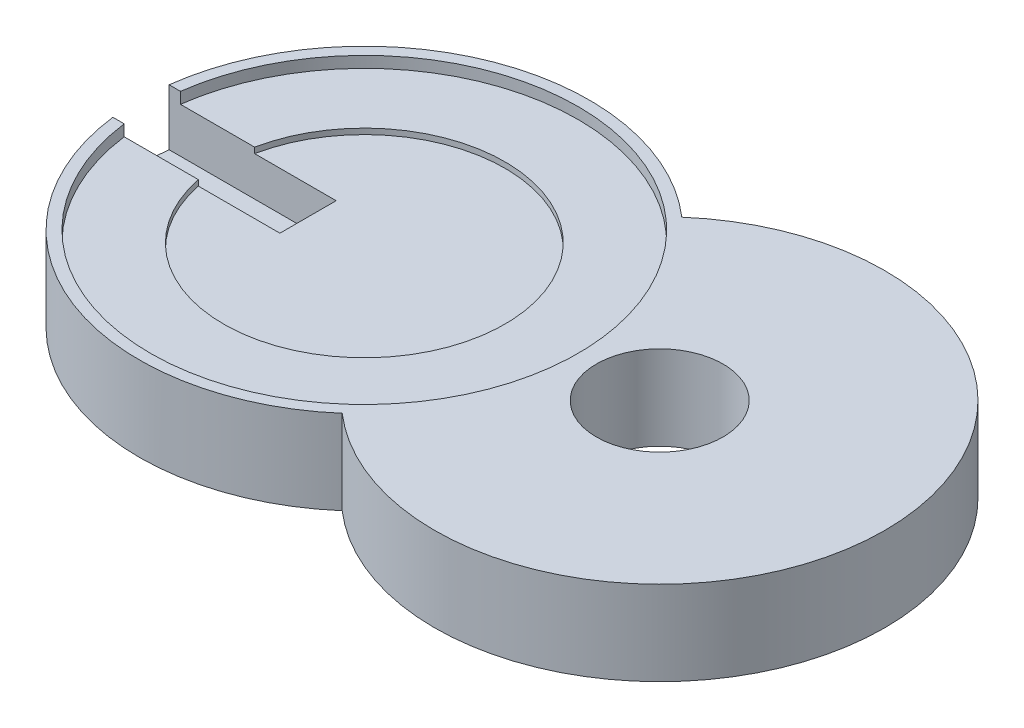
SolidWorks part; units mm, degrees
ref_plane "前视基准面" through (0, 0, 0) normal (0, 0, 1) x (1, 0, 0)
ref_plane "上视基准面" through (0, 0, 0) normal (0, 1, 0) x (1, 0, 0)
ref_plane "右视基准面" through (0, 0, 0) normal (1, 0, 0) x (0, 0, -1)
other "Configuration Table"
sketch "草图1" plane through (0, 0, 0) normal (0, 1, 0) x (1, 0, 0)
  arc A0 (-5.25, -6.0363) -> (-5.25, 6.0363) centre (0, 0) ccw
  circle A1 centre (0, 0) radius 2.25
  arc A2 (-5.25, 6.0363) -> (-5.25, -6.0363) centre (-10.5, 0) ccw
  dimension "D1" = 16
  dimension "D2" = 4.5
  dimension "D4" = 16
  dimension "D3" = 10.5
extrude "凸台-拉伸1" add sketch "草图1" along normal blind 3
sketch "草图5" plane through (0, 3, 0) normal (0, 1, 0) x (1, 0, 0)
  circle A0 centre (-10.5, 0) radius 7.6
  dimension "D1" = 15.2
extrude "切除-拉伸3" cut sketch "草图5" against normal blind 0.4
sketch "草图6" plane through (0, 3, 0) normal (0, 1, 0) x (1, 0, 0)
  line L1 (-12.5, 1) -> (-21.5051, 1)
  line L2 (-12.5, 1) -> (-12.5, -1)
  line L3 (-12.5, -1) -> (-21.5051, -1)
  line L4 (-21.5051, 1) -> (-21.5051, -1)
  circle A0 centre (-10.5, 0) radius 7.6 construction
  dimension "D1" = 2
  dimension "D2" = 1
  dimension "D3" = 2
extrude "切除-拉伸4" cut sketch "草图6" against normal blind 2
sketch "草图7" plane through (0, 2.6, 0) normal (0, 1, 0) x (1, 0, 0)
  circle A0 centre (-10.5, 0) radius 5
  dimension "D1" = 10
extrude "切除-拉伸5" cut sketch "草图7" against normal blind 0.2
